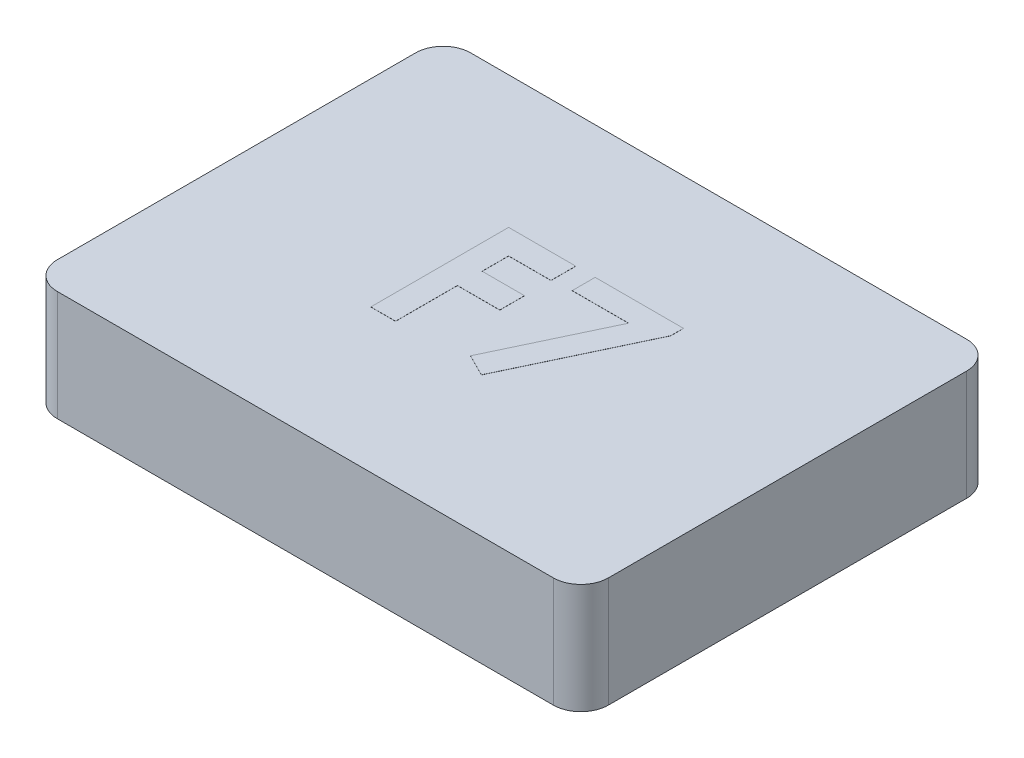
SolidWorks part; units mm, degrees
ref_plane "Front Plane" through (0, 0, 0) normal (0, 0, 1) x (1, 0, 0)
ref_plane "Top Plane" through (0, 0, 0) normal (0, 1, 0) x (1, 0, 0)
ref_plane "Right Plane" through (0, 0, 0) normal (1, 0, 0) x (0, 0, -1)
sketch "Sketch1" plane through (0, 0, 0) normal (0, 1, 0) x (1, 0, 0)
  line L0 (0, 0) -> (12.7, 0)
  line L1 (12.7, 0) -> (12.7, 9.525)
  line L2 (12.7, 9.525) -> (0, 9.525)
  line L3 (0, 9.525) -> (0, 0)
  dimension "D1" = 12.7
  dimension "D2" = 9.525
extrude "Boss-Extrude1" add sketch "Sketch1" along normal blind 2.54
fillet "Fillet1" radius 0.635 4 edges at (0, 1.27, -9.525) (12.7, 1.27, -9.525) (12.7, 1.27, 0) (0, 1.27, 0)
shell "Shell1" thickness 0.635 removed face at (6.35, 0, -4.7625)
sketch "Sketch2" plane through (0, 1.905, 0) normal (0, -1, 0) x (-1, 0, 0)
  line L0 (-0.635, 4.7625) -> (-12.065, 4.7625) construction
  line L1 (-0.635, 8.89) -> (-0.635, 0.635) construction
  line L2 (-12.065, 0.635) -> (-12.065, 8.89) construction
  line L3 (-6.35, 0.635) -> (-6.35, 8.89) construction
  line L4 (-0.635, 0.635) -> (-12.065, 0.635) construction
  line L5 (-12.065, 8.89) -> (-0.635, 8.89) construction
  circle A0 centre (-6.35, 4.7625) radius 2.54
  dimension "D1" = 5.08
extrude "Boss-Extrude2" add sketch "Sketch2" along normal up to surface (1.905 mm away) up to face at (6.35, 0, -4.7625)
sketch "Sketch3" plane through (0, 2.54, 0) normal (0, 1, 0) x (1, 0, 0)
  line L0 (0.635, 0) -> (12.065, 0) construction
  line L1 (0, 8.89) -> (0, 0.635) construction
  text T0 "<b>F7</b>"
  dimension "D1" = 3.302
  dimension "D2" = 4.191
extrude "Boss-Extrude3" add sketch "Sketch3" along normal blind 0.0025
